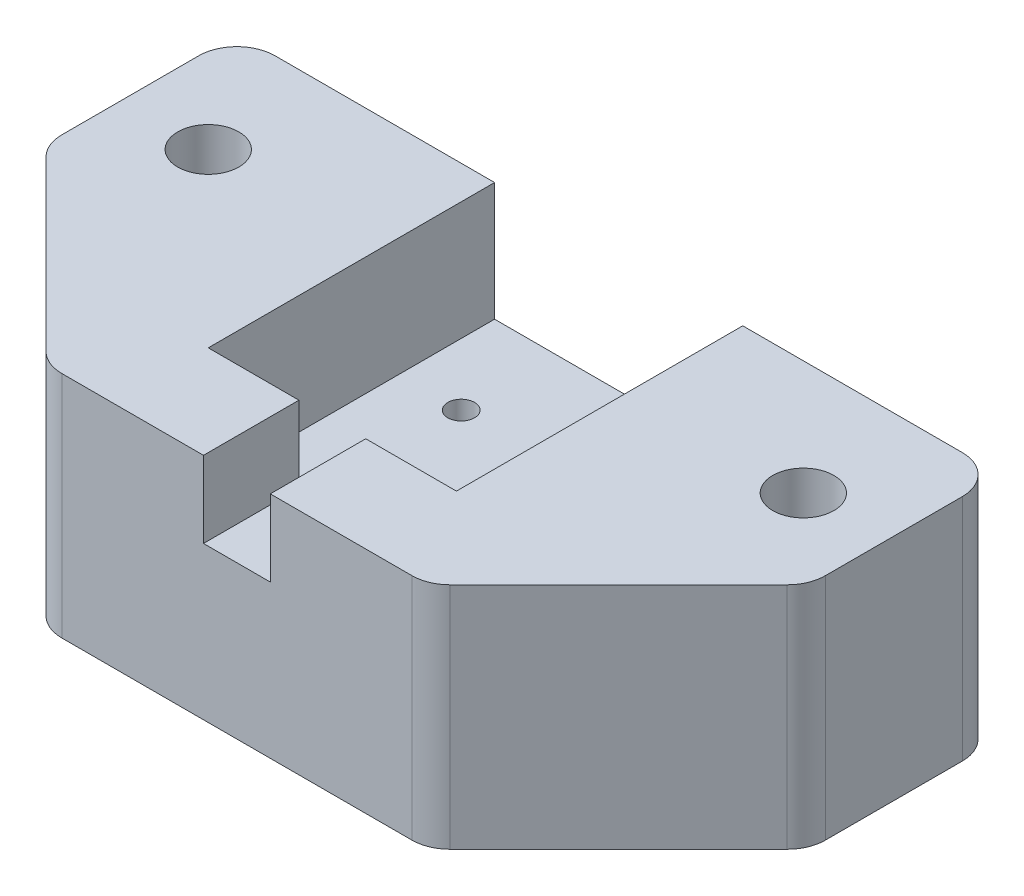
SolidWorks part; units mm, degrees
ref_plane "前视基准面" through (0, 0, 0) normal (0, 0, 1) x (1, 0, 0)
ref_plane "上视基准面" through (0, 0, 0) normal (0, 1, 0) x (1, 0, 0)
ref_plane "右视基准面" through (0, 0, 0) normal (1, 0, 0) x (0, 0, -1)
other "Configuration Table"
sketch "草图1" plane through (0, 0, 0) normal (0, 1, 0) x (1, 0, 0)
  line L1 (0, 0) -> (40, 0)
  line L2 (0, 0) -> (0, -20)
  line L3 (0, -20) -> (40, -20)
  line L4 (40, 0) -> (40, -20)
  circle A0 centre (4.5, -6) radius 1.6
  circle A1 centre (35.6729, -6) radius 1.6
  point P9 (0, 0)
  point P10 (0, 0)
  point P11 (0, -8.3178)
  point P13 (6.1682, 0)
  dimension "D3" = 3.2
  dimension "D4" = 3.2
  dimension "D1" = 40
  dimension "D2" = 20
  dimension "D5" = 35.6729
  dimension "D6" = 4.5
  dimension "D7" = 6
  dimension "D8" = 6
extrude "凸台-拉伸1" add sketch "草图1" along normal blind 12
sketch "草图2" plane through (0, 12, 0) normal (0, 1, 0) x (1, 0, 0)
  line L5 (0, 0) -> (0, -20) construction
  line L6 (40, 0) -> (0, 0) construction
  line L8 (13.5, 0) -> (26.5, 0)
  line L9 (13.5, 0) -> (13.5, -15)
  line L10 (13.5, -15) -> (26.5, -15)
  line L11 (26.5, 0) -> (26.5, -15)
  dimension "D4" = 15
  dimension "D5" = 13
  dimension "D6" = 13.5
extrude "切除-拉伸1" cut sketch "草图2" against normal blind 6.2
sketch "草图3" plane through (0, 12, 0) normal (0, 1, 0) x (1, 0, 0)
  line L0 (13.5, -15) -> (26.5, -15) construction
  line L1 (18.25, -15) -> (21.75, -15)
  line L2 (18.25, -15) -> (18.25, -20)
  line L3 (18.25, -20) -> (21.75, -20)
  line L4 (21.75, -15) -> (21.75, -20)
  line L5 (0, -20) -> (40, -20) construction
  line L6 (0, 0) -> (0, -20) construction
  dimension "D1" = 3.5
  dimension "D2" = 18.25
extrude "切除-拉伸2" cut sketch "草图3" against normal blind 4
chamfer "倒角1" distance 10 angle 45 2 edges at (40, 6, 20) (0, 6, 20)
fillet "圆角1" radius 2 6 edges at (0, 6, 0) (0, 6, 10) (10, 6, 20) (30, 6, 20) (40, 6, 10) (40, 6, 0)
sketch "草图4" plane through (0, 5.8, 0) normal (0, 1, 0) x (1, 0, 0)
  line L0 (26.5, 0) -> (13.5, 0) construction
  line L1 (13.5, 0) -> (13.5, -15) construction
  circle A0 centre (16.75, -5) radius 0.7
  circle A1 centre (23.25, -5) radius 0.7
  point P4 (0, 0)
  point P6 (17.0406, 0)
  dimension "D1" = 1.4
  dimension "D2" = 1.4
  dimension "D3" = 5
  dimension "D4" = 5
  dimension "D5" = 6.5
  dimension "D6" = 3.25
extrude "切除-拉伸3" cut sketch "草图4" against normal through all
sketch "草图5" plane through (0, 0, 0) normal (0, -1, 0) x (-1, 0, 0)
  circle A0 centre (-35.6729, -6) radius 3
  circle A1 centre (-4.5, -6) radius 3
  dimension "D1" = 6
  dimension "D2" = 6
extrude "切除-拉伸4" cut sketch "草图5" against normal blind 4
chamfer "倒角2" distance 2 angle 45 2 edges at (35.6729, 4, 4.4) (4.5, 4, 4.4)
equation "\"D6@草图1\"=20-31/2"
equation "\"D6@草图2\"=20-13/2"
equation "\"D2@草图3\"=20-3.5/2"
equation "\"D6@草图4\"=6.5/2"
